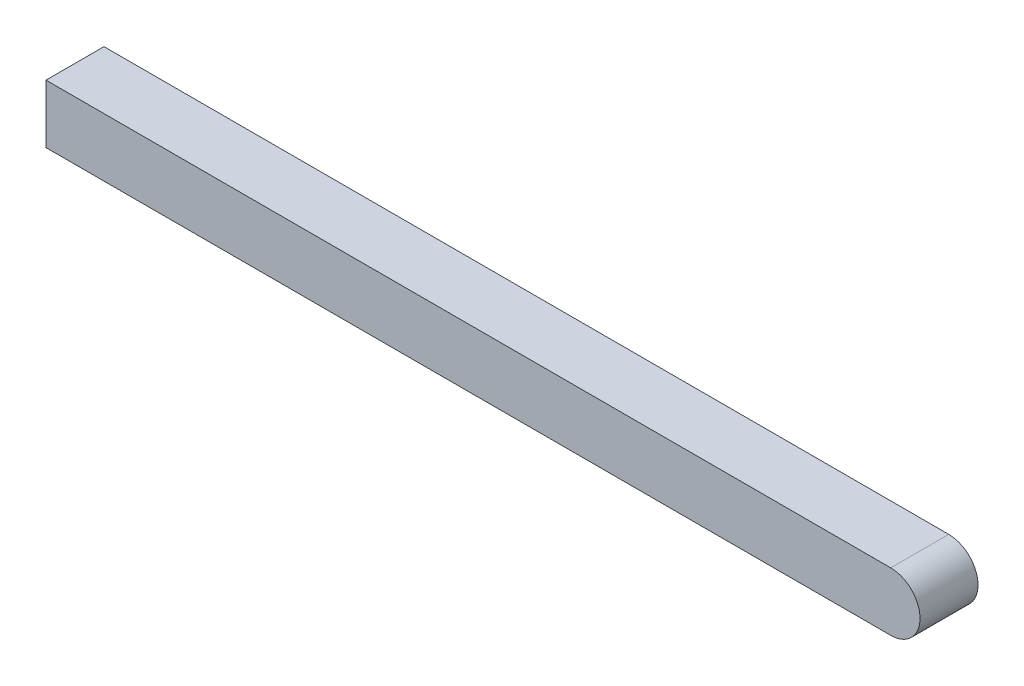
SolidWorks part; units mm, degrees
ref_plane "Спереди" through (0, 0, 0) normal (0, 0, 1) x (1, 0, 0)
ref_plane "Сверху" through (0, 0, 0) normal (0, 1, 0) x (1, 0, 0)
ref_plane "Справа" through (0, 0, 0) normal (1, 0, 0) x (0, 0, -1)
other "Configuration Table"
sketch "Ширина_фанера_плюс_зазор" plane through (0, 0, 0) normal (0, 0, 1) x (1, 0, 0)
  line L0 (-0.1, -9.075) -> (262.075, -9.075)
  line L1 (262.075, -9.075) -> (262.075, 9.075)
  line L2 (262.075, 9.075) -> (-0.1, 9.075)
  line L3 (-0.1, 9.075) -> (-0.1, -9.075)
  line L4 (-0.1, -9.075) -> (262.075, 9.075) construction
  point P4 (130.9875, 0)
  dimension "Ширина" = 262.175
  dimension "Глубина" = 18.15
  dimension "Положение_ПоОси" = 130.9875
extrude "Прямой_участок" add sketch "Ширина_фанера_плюс_зазор" along normal blind 18
sketch "Выход_фрезы6" plane through (0, 0, 0) normal (0, 0, 1) x (1, 0, 0)
  circle A0 centre (262.075, 0) radius 9.075
  dimension "Диаметр1" = 18.15
  dimension "Центр1_ПоОси" = 262.075
extrude "Круглый_конец" add sketch "Выход_фрезы6" along normal blind 18
equation "\"Диаметр1@Выход_фрезы6\"  = \"Толщина горизонтальных плит\"+\"Посадочный зазор\""
equation "\"Глубина@Ширина_фанера_плюс_зазор\"  = \"Толщина горизонтальных плит\"+\"Посадочный зазор\""
equation "\"Фанера\"= \"Толщина горизонтальных плит\""
equation "\"Ширина шипа\"=16"
equation "\"Межосевое шипов\"=40"
equation "\"Посадочный зазор\"=0.15"
equation "\"Основная фреза\"=6"
equation "\"Мелкая фреза\"=6"
equation "\"Запас разгрузки\"=0.05"
equation "\"Ширина образца\"=84"
equation "\"Высота образца\"=50"
equation "\"Канал М6\"=6"
equation "\"Гайка под ключ\"=10.3"
equation "\"Длина кармана гайки\"=6.2"
equation "\"Отступ гайки\"=12"
equation "\"Ширина@Ширина_фанера_плюс_зазор\" = 262.175"
equation "\"Положение_ПоОси@Ширина_фанера_плюс_зазор\" =  ( 130.9875 ) "
equation "\"Центр1_ПоОси@Выход_фрезы6\" =  ( 262.075 ) "
equation "\"Ширина груза\"= 420"
equation "\"Глубина груза\"= 490"
equation "\"Высота груза\"= 297"
equation "\"Ширина ячейки\"= \"Ширина груза\" + 10"
equation "\"Глубина ячейки\"= \"Глубина груза\" + 10"
equation "\"Высота ячейки\"= \"Высота груза\" + 10 + 13"
equation "\"Колво ячеек ширина\"= 2"
equation "\"Колво ячеек высота\"= 2"
equation "\"Толщина стенки\" = \"Толщина тонких панелей\""
equation "\"Крепление дверцы\"= 5 "
equation "\"Ширина рейки\"= \"Толщина шестерни\""
equation "\"Высота рейки\"= 20"
equation "\"Высота пола\" = 2*\"Толщина тонких панелей\""
equation "\"Колво полозьев\"= 5"
equation "\"Отступ рейки\"= 20"
equation "\"Глубина каретки\"= \"Глубина ячейки\" + 30 + \"Мотор Y высота корпуса\" + 20"
equation "\"Длинна рейки\" = (\"Ширина ячейки\"+\"Толщина вертикальных стенок\"+\"Крепление дверцы\")*\"Колво ячеек ширина\"+\"Ширина ячейки выгрузки\"*\"Колво выгрузки\"+\"Толщина вертикальных стенок\"+2*\"Отступ крепления мотора фиксации\"-\"Крепление дверцы\"*\"Колво ячеек ширина\""
equation "\"Отступ шпильки\"= 26"
equation "\"Диаметр шпильки\"= 5"
equation "\"Длинна шпильки\" = (\"Высота ячейки\"+\"Толщина горизонтальных плит\"+\"Высота пола\")*\"Колво ячеек высота\"+2*(\"Толщина горизонтальных плит\"+\"Отступ рейки\")"
equation "\"Ширина пластины\"= 50  "
equation "\"Высота зона выгрузки\"= \"Высота ячейки\" * 2 + \"Толщина стенки\" * 2"
equation "\"Колво выгрузки\"= 1"
equation "\"Ширина ячейки выгрузки\" = \"Ширина ячейки\"+\"Толщина вертикальных стенок\"+2*\"Отступ крепления мотора фиксации\""
equation "\"Отступ крепления мотора фиксации\" = (\"Ширина пластины\"+20-\"Толщина вертикальных стенок\")/2"
equation "\"Мотор X ширина корпуса\"= 42.3"
equation "\"Мотор X высота корпуса\"= 42.3"
equation "\"Мотор X длина корпуса\"= 40"
equation "\"Мотор X вылет вала\"= 19.8"
equation "\"Мотор Y ширина корпуса\"= 42.3"
equation "\"Мотор Y высота корпуса\"= 42.3"
equation "\"Мотор Y длина корпуса\"= 48"
equation "\"Мотор Y вылет вала\"= 30"
equation "\"Мотор Z ширина корпуса\"= 42"
equation "\"Мотор Z высота корпуса\"= 42"
equation "\"Мотор Z длина корпуса\"= 40"
equation "\"Мотор Z вылет вала\"= 23"
equation "\"Мотор диаметр вала ПРЕДВ\"= 5"
equation "\"Мотор шаг крепления ПРЕДВ\"= 31"
equation "\"Мотор диаметр отверстий ПРЕДВ\"= 3"
equation "\"Мотор глубина отверстий ПРЕДВ\"= 4.5"
equation "\"Мотор диаметр буртика ПРЕДВ\"= 22"
equation "\"Мотор высота буртика ПРЕДВ\"= 2"
equation "\"Мотор диаметр шкива ПРЕДВ\"= 16"
equation "\"Мотор длина шкива ПРЕДВ\"= 12"
equation "\"Мотор отступ шкива ПРЕДВ\"= 5"
equation "\"Мотор X шаг градусов\"= 1.8"
equation "\"Мотор Y шаг градусов\"= 1.8"
equation "\"Мотор Z шаг градусов\"= 1.8"
equation "\"Мотор Y диаметр ротора\"= 25.78"
equation "\"Толщина шестерни\"= 10"
equation "\"Толщина тонких панелей\"= 6"
equation "\"Толщина вертикальных стенок\"= 18"
equation "\"Толщина горизонтальных плит\"= 18"
equation "\"Базовая высота корпуса\"= (\"Высота ячейки\"+\"Толщина тонких панелей\"+\"Высота пола\")*\"Колво ячеек высота\"+6*\"Толщина тонких панелей\"+\"Мотор X ширина корпуса\"+\"Мотор Y ширина корпуса\"+75"
equation "\"Высота корпуса\"= (\"Высота ячейки\"+\"Толщина горизонтальных плит\"+\"Высота пола\")*\"Колво ячеек высота\"+2*\"Толщина горизонтальных плит\"+4*\"Толщина тонких панелей\"+\"Мотор X ширина корпуса\"+\"Мотор Y ширина корпуса\"+75"
equation "\"Смещение центра корпуса\"= (\"Высота корпуса\"-\"Базовая высота корпуса\")/2-(\"Толщина горизонтальных плит\"-\"Толщина тонких панелей\")"
equation "\"Отметка пола\"= -\"Базовая высота корпуса\"/2+\"Толщина тонких панелей\""
equation "\"Отметка потолка\"= \"Отметка пола\"+\"Высота корпуса\"-2*\"Толщина горизонтальных плит\""
equation "\"Отметка верхней полки\"= \"Отметка потолка\"-(28+\"Толщина тонких панелей\")-\"Высота ячейки\"-\"Высота пола\""
equation "\"Отметка нижней полки\"= \"Отметка верхней полки\"-\"Высота ячейки\"-\"Высота пола\"-\"Толщина горизонтальных плит\""
